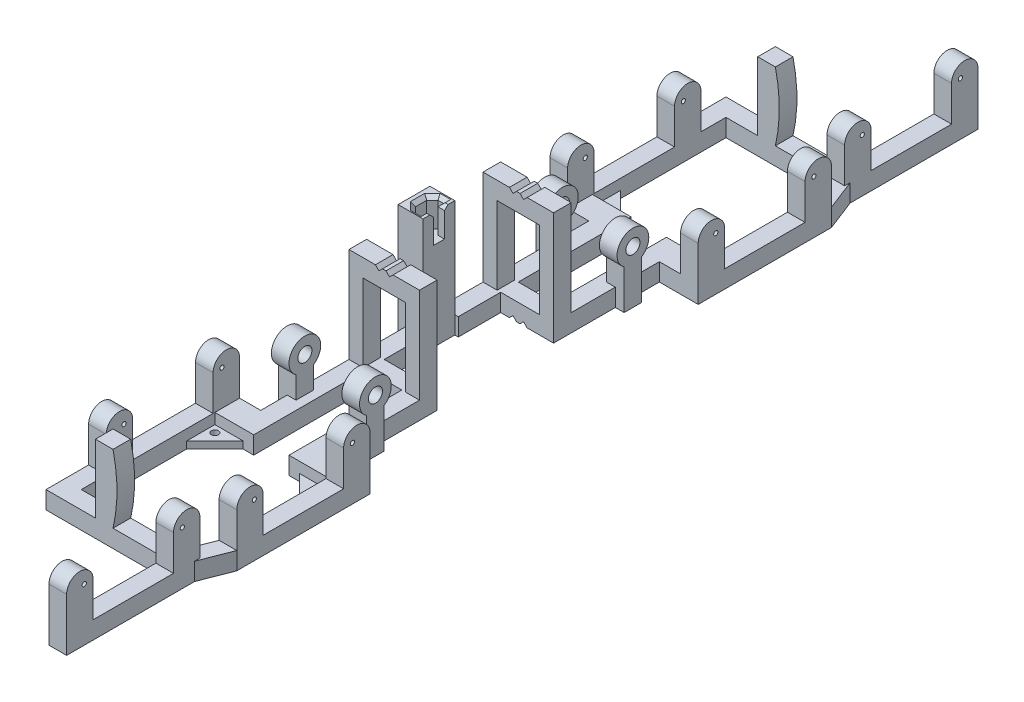
SolidWorks part; units mm, degrees
ref_plane "Спереди" through (0, 0, 0) normal (0, 0, 1) x (1, 0, 0)
ref_plane "Сверху" through (0, 0, 0) normal (0, 1, 0) x (1, 0, 0)
ref_plane "Справа" through (0, 0, 0) normal (1, 0, 0) x (0, 0, -1)
sketch "Эскиз2" plane through (0, 0, 0) normal (0, 0, 1) x (1, 0, 0)
  line L0 (1.5, 32) -> (1.5, 31) construction
  line L1 (0, 0) -> (0.5, 0)
  line L2 (0, 0) -> (0, 5)
  line L3 (0, 32) -> (10, 32)
  line L4 (10, 0) -> (10, 32)
  line L5 (10, 0) -> (5, 0)
  line L6 (10, 0) -> (10, 5)
  line L7 (10, 5) -> (5, 5)
  line L8 (5, 0) -> (5, 5)
  line L9 (6, 5) -> (0, 5)
  line L10 (6, 5) -> (6, 27)
  line L11 (6, 27) -> (0, 27)
  line L12 (1.5, 1) -> (2.5, 0)
  line L13 (1.5, 31) -> (2.5, 32)
  line L14 (1.5, 31) -> (0.5, 32)
  line L15 (10, 16) -> (6, 16) construction
  line L16 (0, 27) -> (0, 32)
  line L17 (1.5, 1) -> (0.5, 0)
  line L18 (2.5, 0) -> (10, 0)
  dimension "D1" = 10
  dimension "D2" = 32
  dimension "D3" = 5
  dimension "D4" = 5
  dimension "D5" = 22
  dimension "D6" = 6
  dimension "D7" = 1.5
  dimension "D8" = 1
extrude "Rail1" add sketch "Эскиз2<5>" against normal blind 27.5 contours L6 L7 L8 L5
sketch "Эскиз2<5>" plane through (0, 0, 0) normal (0, 0, 1) x (1, 0, 0) same geometry as "Эскиз2"
extrude "ArchForThread1" add sketch "Эскиз2" along normal mid plane 5 contours L16 L11 L10 L7 L4 L3 L13 L14 | L12 L18 L8 L9 L2 L1 L17 region at (2.5417, 2.5903, 0) region at (6.9526, 20.8127, 0)
mirror "Зеркальное отражение2" about plane through (0, 0, 0) normal (1, 0, 0) of "ArchForThread1"
mirror "Зеркальное отражение3" about plane through (0, 0, 0) normal (1, 0, 0) of "Rail1"
extrude "Rail2" add sketch "Эскиз2<6>" along normal blind 2.5 contours L8 L5 L4 L7 region at (7.5, 2.5, 0)
sketch "Эскиз2<6>" plane through (0, 0, 0) normal (0, 0, 1) x (1, 0, 0) same geometry as "Эскиз2"
sketch "Эскиз3" plane through (0, 0, 0) normal (0, 0, 1) x (1, 0, 0)
  line L1 (-5, 0) -> (-10, 0)
  line L2 (-5, 0) -> (-5, 5)
  line L3 (-5, 5) -> (-10, 5)
  line L4 (-10, 0) -> (-10, 5)
extrude "CellNest" add sketch "Эскиз3" along normal blind 14.5
sketch "Эскиз4" plane through (0, 0, 0) normal (0, 1, 0) x (1, 0, 0)
  line L0 (-5, -19) -> (-6, -19) construction
  line L1 (-6, -14.5) -> (-13.05, -14.5)
  line L2 (-5, -19) -> (-5, -14.5) construction
  line L3 (-6, -23.5) -> (-13.05, -23.5)
  line L4 (-13.05, -14.5) -> (-13.05, -23.5)
  line L5 (-6, -14.5) -> (-6, -23.5)
  line L6 (-5, -23.5) -> (-5, -19) construction
  line L7 (-5, -14.5) -> (-6, -14.5) construction
  line L8 (-5, -23.5) -> (-6, -23.5) construction
  dimension "D1" = 9
  dimension "D2" = 8.05
  dimension "D3" = 1
extrude "Бобышка-Вытянуть6" add sketch "Эскиз4" along normal blind 25
sketch "Эскиз5" plane through (0, 25, 0) normal (0, 1, 0) x (1, 0, 0)
  line L0 (-13.05, -19) -> (-11.05, -19) construction
  line L1 (-13.05, -23.5) -> (-6, -23.5)
  line L2 (-13.05, -23.5) -> (-13.05, -14.5)
  line L3 (-13.05, -14.5) -> (-6, -14.5)
  line L4 (-6, -23.5) -> (-6, -20.6)
  line L5 (-11.05, -17.4) -> (-11.05, -20.6)
  line L6 (-11.05, -20.6) -> (-9.45, -22.2)
  line L7 (-9.45, -22.2) -> (-7.85, -22.2)
  line L8 (-7.85, -22.2) -> (-7.85, -20.6)
  line L9 (-7.85, -20.6) -> (-6, -20.6)
  line L10 (-7.85, -17.4) -> (-6, -17.4)
  line L11 (-7.85, -15.8) -> (-7.85, -17.4)
  line L12 (-9.45, -15.8) -> (-7.85, -15.8)
  line L13 (-11.05, -17.4) -> (-9.45, -15.8)
  line L14 (-6, -14.5) -> (-6, -17.4)
  dimension "D1" = 2
  dimension "D2" = 1.6
  dimension "D3" = 1.85
  dimension "D4" = 1.6
  dimension "D5" = 1.6
  dimension "D6" = 2.9
  dimension "D7" = 7.05
extrude "Бобышка-Вытянуть7" add sketch "Эскиз5" along normal blind 8
chamfer "Фаска1" distance 1 angle 45 9 edges at (-6.925, 33, 20.6) (-7.85, 33, 21.4) (-8.65, 33, 22.2) (-10.25, 33, 21.4) (-6.925, 33, 17.4) (-7.85, 33, 16.6) (-8.65, 33, 15.8) (-10.25, 33, 16.6) (-11.05, 33, 19)
sketch "Эскиз6" plane through (0, 0, 0) normal (0, 1, 0) x (1, 0, 0)
  line L0 (-10, 0) -> (10, 0) construction
  line L1 (-10, -2.5) -> (-10, 2.5) construction
  line L2 (10, -2.5) -> (10, 2.5) construction
sketch "Эскиз7" plane through (10, 0, 0) normal (1, 0, 0) x (0, 0, -1)
  line L0 (0, 0) -> (17.5, 0) construction
  line L1 (27.5, 0) -> (-2.5, 0) construction
  line L2 (17.5, 0) -> (17.5, 15) construction
  line L3 (20, 11.2583) -> (20, 0)
  line L4 (20, 0) -> (15, 0)
  line L5 (15, 11.2583) -> (15, 0)
  circle A0 centre (17.5, 15) radius 2
  arc A1 (20, 11.2583) -> (15, 11.2583) centre (17.5, 15) ccw
  dimension "D3" = 9
  dimension "D4" = 4
  dimension "D1" = 17.5
  dimension "D2" = 15
  dimension "D5" = 2.5
extrude "Бобышка-Вытянуть8" add sketch "Эскиз7" along normal mid plane 5
mirror "Зеркальное отражение4" about plane through (0, 0, 0) normal (1, 0, 0) of "Бобышка-Вытянуть8"
sketch "Эскиз12" plane through (0, 0, 0) normal (0, 1, 0) x (1, 0, 0)
  line L1 (5, 27.5) -> (21, 27.5)
  line L2 (5, 27.5) -> (5, 34.5)
  line L3 (5, 34.5) -> (21, 34.5)
  line L4 (21, 27.5) -> (21, 34.5)
  dimension "D1" = 7
  dimension "D2" = 16
extrude "Бобышка-Вытянуть9" add sketch "Эскиз12" along normal blind 5
sketch "Эскиз13" plane through (21, 0, 0) normal (1, 0, 0) x (0, 0, -1)
  line L0 (27.5, 15) -> (35, 15) construction
  line L1 (27.5, 0) -> (65.3, 0)
  line L2 (27.5, 0) -> (27.5, 15)
  line L3 (35, 15) -> (35, 5) construction
  line L4 (65.3, 0) -> (65.3, 15)
  line L5 (27.5, 5) -> (34.5, 5) construction
  line L6 (31.25, 18.5) -> (31.25, 15) construction
  line L7 (35, 15) -> (35, 5)
  line L8 (46.4, 0) -> (46.4, 5) construction
  line L9 (57.8, 15) -> (57.8, 5)
  line L10 (65.3, 0) -> (65.3, 15)
  line L11 (35, 5) -> (57.8, 5)
  line L12 (31.25, 15) -> (32.5, 15) construction
  arc A0 (35, 15) -> (27.5, 15) centre (31.25, 15) ccw
  circle A1 centre (32.5, 15) radius 0.6
  circle A2 centre (60.3, 15) radius 0.6
  arc A3 (57.8, 15) -> (65.3, 15) centre (61.55, 15) cw
  line M1 (27.5, 0) -> (34.5, 0)
  line M2 (34.5, 0) -> (34.5, 5)
  line M3 (34.5, 5) -> (27.5, 5)
  line M4 (27.5, 5) -> (27.5, 0)
  dimension "D5" = 5
  dimension "D6" = 1.2
  dimension "D1" = 15
  dimension "D2" = 37.8
  dimension "D3" = 7.5
  dimension "D4" = 3.5
extrude "Бобышка-Вытянуть10" add sketch "Эскиз13" against normal blind 5 contours A3 L9 L11 L1 L4 M2 | M4 M1 M2 M3 | L7 A0 L2 M3 region at (21, 2.5, -31) region at (21, 2.5, -34.9219)
mirror "Зеркальное отражение5" about plane through (0, 0, 0) normal (1, 0, 0) of "Бобышка-Вытянуть9", "Бобышка-Вытянуть10"
sketch "Эскиз14" plane through (0, 0, 0) normal (0, 1, 0) x (1, 0, 0)
  line L0 (21, 65.3) -> (21, 74.3) construction
  line L1 (21, 74.3) -> (17.5, 74.3) construction
  line L2 (21, 65.3) -> (17.5, 74.3)
  line L3 (21, 65.3) -> (16, 65.3)
  line L4 (17.5, 74.3) -> (12.5, 74.3)
  line L5 (16, 65.3) -> (12.5, 74.3)
  line L6 (21, 27.5) -> (17.5, 74.3) construction
  dimension "D1" = 3.5
  dimension "D2" = 9
  dimension "D3" = 5
  dimension "D4" = 46.9307
extrude "Бобышка-Вытянуть11" add sketch "Эскиз14" along normal blind 5
pattern_linear "Линейный массив1" count 2 spacing 45 along (-0.0746, 0, -0.9972) of "Бобышка-Вытянуть10"
sketch "Эскиз15" plane through (0, 0, 0) normal (0, 1, 0) x (1, 0, 0)
  line L0 (-16, 72.3747) -> (-21.0002, 72.3747) construction
  line L1 (13.2487, 72.3747) -> (-16, 72.3747)
  line L2 (13.2487, 72.3747) -> (13.2487, 77.3747)
  line L3 (13.2487, 77.3747) -> (-21.0002, 77.3747)
  line L4 (-21.0002, 72.3747) -> (-21.0002, 77.3747)
  line L6 (-21.0002, 72.3747) -> (-21.0002, 65.3)
  line L7 (-21.0002, 65.3) -> (-16, 65.3)
  line L8 (-16, 72.3747) -> (-16, 65.3)
  dimension "D1" = 5
extrude "Бобышка-Вытянуть12" add sketch "Эскиз15" along normal blind 5
sketch "Эскиз16" plane through (0, 0, -77.3747) normal (0, 0, -1) x (-1, 0, 0)
  line L0 (7.0002, 5) -> (21.0002, 5) construction
  line L1 (-12.644, 5) -> (21.0002, 5) construction
  line L2 (2.0002, 5) -> (7.0002, 5)
  line L3 (2.0002, 5) -> (2.0002, 24.3705)
  line L4 (2.0002, 24.3705) -> (7.0002, 24.3705)
  line L7 (7.0002, 5) -> (7.0002, 24.3705)
  arc A0 (2.0002, 5) -> (2.0002, 24.3705) centre (43.3569, 14.6852) cw
  line M1 (21.0002, 5) -> (-12.644, 5)
  dimension "D1" = 5
  dimension "D2" = 14
extrude "Бобышка-Вытянуть13" add sketch "Эскиз16" against normal blind 5 contours A0 L3 | L7 L4 L3 M1 region at (-4.5002, 14.6852, -77.3747) region at (-1.5521, 14.6852, -77.3747)
sketch "Эскиз17" plane through (0, 33, 0) normal (0, 1, 0) x (1, 0, 0)
  line L0 (-13.05, -14.5) -> (-13.05, -23.5) construction
  point P0 (-13.05, -19)
ref_plane "Плоскость1" through (0, 0, 19) normal (0, 0, 1) x (1, 0, 0)
mirror "Зеркальное отражение8" about plane through (0, 0, 19) normal (0, 0, 1) of "CellNest"
mirror "Зеркальное отражение13" about plane through (0, 0, 19) normal (0, 0, 1) of "Зеркальное отражение2"
mirror "Зеркальное отражение19" about plane through (0, 0, 19) normal (0, 0, 1) of "Rail1"
mirror "Зеркальное отражение20" about plane through (0, 0, 19) normal (0, 0, 1) of "Rail2"
mirror "Зеркальное отражение21" about plane through (0, 0, 0) normal (1, 0, 0) of "Зеркальное отражение19", "Зеркальное отражение20"
mirror "Зеркальное отражение22" about plane through (0, 0, 19) normal (0, 0, 1) of "Зеркальное отражение4"
mirror "Зеркальное отражение23" about plane through (0, 0, 19) normal (0, 0, 1) of "Зеркальное отражение5"
mirror "Зеркальное отражение24" about plane through (0, 0, 19) normal (0, 0, 1) of "Бобышка-Вытянуть11"
mirror "Зеркальное отражение25" about plane through (0, 0, 19) normal (0, 0, 1) of "Линейный массив1"
mirror "Зеркальное отражение26" about plane through (0, 0, 19) normal (0, 0, 1) of "Бобышка-Вытянуть13", "Бобышка-Вытянуть12"
sketch "Эскиз18" plane through (0, 0, 0) normal (0, 1, 0) x (1, 0, 0)
  line L0 (16, 34.5) -> (8, 34.5)
  line L1 (16, 34.5) -> (5, 34.5) construction
  line L2 (8, 34.5) -> (16, 42.5)
  line L3 (16, 35) -> (16, 57.8) construction
  line L4 (16, 42.5) -> (16, 34.5)
  line L5 (12, 38.5) -> (16, 34.5) construction
  circle A0 centre (14, 36.5) radius 1
  dimension "D3" = 2
  dimension "D1" = 8
  dimension "D2" = 8
extrude "Бобышка-Вытянуть14" add sketch "Эскиз18" along normal blind 2
mirror "ЗеркОтр_ЯзычкиКрепКОснов" about plane through (0, 0, 0) normal (1, 0, 0) of "Бобышка-Вытянуть14"
mirror "ЗеркОтр_ЯзычкиКрепКОснов2" about plane through (0, 0, 19) normal (0, 0, 1) of "ЗеркОтр_ЯзычкиКрепКОснов"
